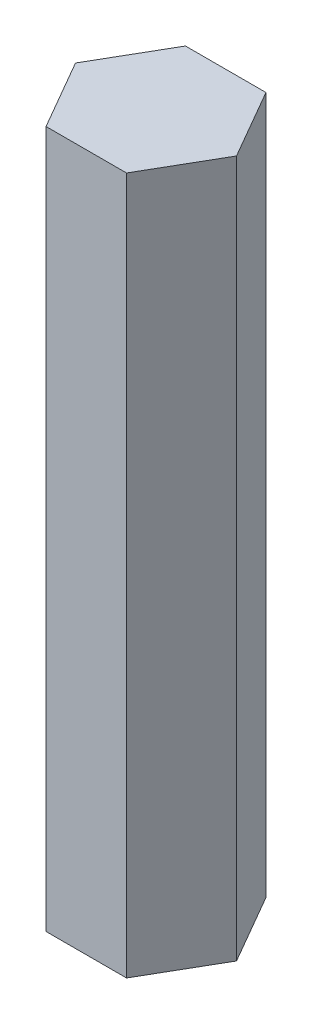
SolidWorks part; units mm, degrees
material "6061-T6 (SS)"
ref_plane "Front" through (0, 0, 0) normal (0, 0, 1) x (1, 0, 0)
ref_plane "Top" through (0, 0, 0) normal (0, 1, 0) x (1, 0, 0)
ref_plane "Right" through (0, 0, 0) normal (1, 0, 0) x (0, 0, -1)
sketch "Sketch1" plane through (0, 0, 0) normal (0, 1, 0) x (1, 0, 0)
  line L1 (7.3323, 0) -> (3.6662, 6.35)
  line L2 (3.6662, 6.35) -> (-3.6662, 6.35)
  line L3 (-3.6662, 6.35) -> (-7.3323, 0)
  line L4 (-7.3323, 0) -> (-3.6662, -6.35)
  line L5 (-3.6662, -6.35) -> (3.6662, -6.35)
  line L6 (3.6662, -6.35) -> (7.3323, 0)
  circle A0 centre (0, 0) radius 6.35 construction
  dimension "D1" = 12.7
extrude "Boss-Extrude1" add sketch "Sketch1" along normal blind 63.5
ref_axis "Axis1" through (0, 50, 0) along (0, -1, 0)
